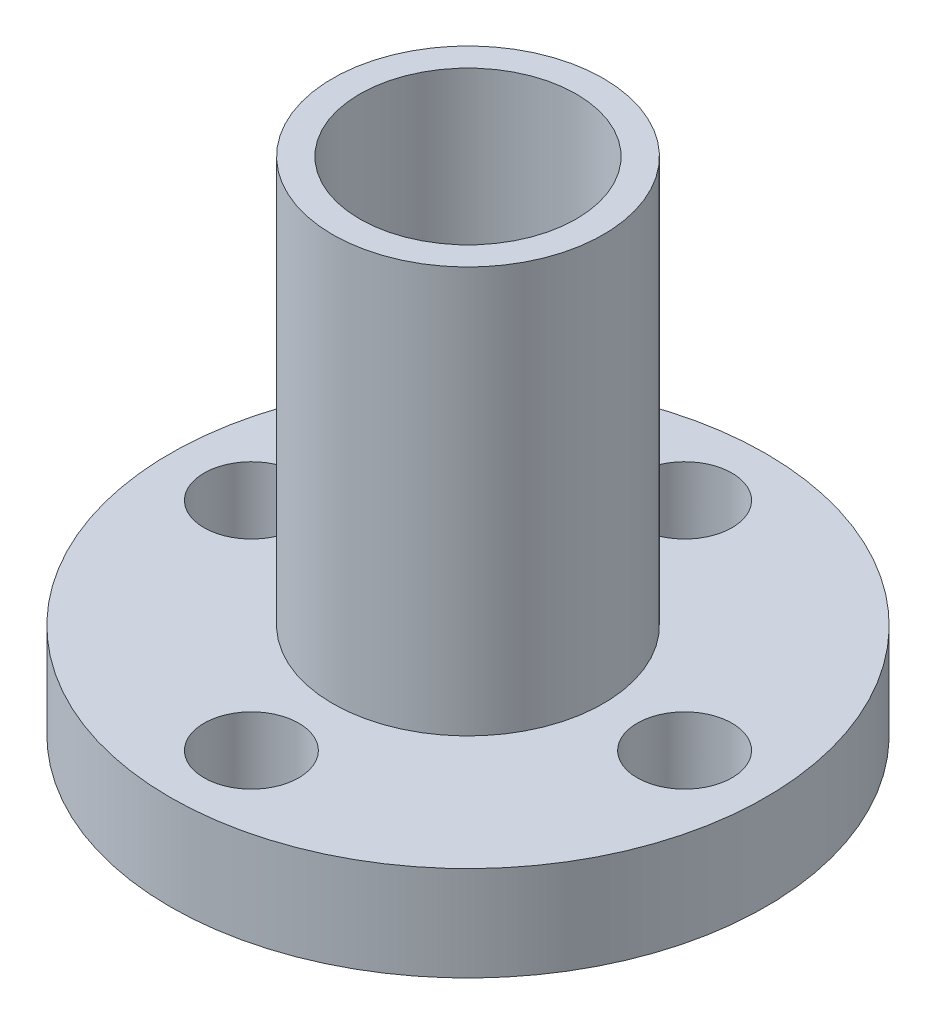
SolidWorks part; units mm, degrees
ref_plane "前视基准面" through (0, 0, 0) normal (0, 0, 1) x (1, 0, 0)
ref_plane "上视基准面" through (0, 0, 0) normal (0, 1, 0) x (1, 0, 0)
ref_plane "右视基准面" through (0, 0, 0) normal (1, 0, 0) x (0, 0, -1)
ref_plane "基准面4" through (0, 1.5, 0) normal (0, -1, 0) x (1, 0, 0)
sketch "草图1" plane through (0, 1.5, 0) normal (0, -1, 0) x (1, 0, 0)
  circle A1 centre (0, 0) radius 11
  dimension "D1" = 22
extrude "凸台-拉伸1" add sketch "草图1" against normal blind 3.5
sketch "草图2" plane through (0, 5, 0) normal (0, 1, 0) x (1, 0, 0)
  circle A0 centre (0, 0) radius 5
  circle A1 centre (0, 0) radius 4
  dimension "D1" = 10
  dimension "D2" = 8
extrude "凸台-拉伸2" add sketch "草图2" along normal blind 15 and the other way blind 5.5
sketch "草图3" plane through (0, 5, 0) normal (0, 1, 0) x (1, 0, 0)
  circle A0 centre (0, 0) radius 8 construction
  circle A1 centre (0, 0) radius 4
  circle A2 centre (0, 0) radius 4
  circle A3 centre (-8, 0) radius 1.75
  circle A4 centre (0, 8) radius 1.75
  circle A5 centre (8, 0) radius 1.75
  circle A6 centre (0, -8) radius 1.75
  point P6 (0, 0)
  point P15 (0, 0)
  dimension "D2" = 16
  dimension "D3" = 3.5
  dimension "D5" = 90
  dimension "D1" = 0
  dimension "D4" = 4
extrude "切除-拉伸1" cut sketch "草图3" against normal through all
